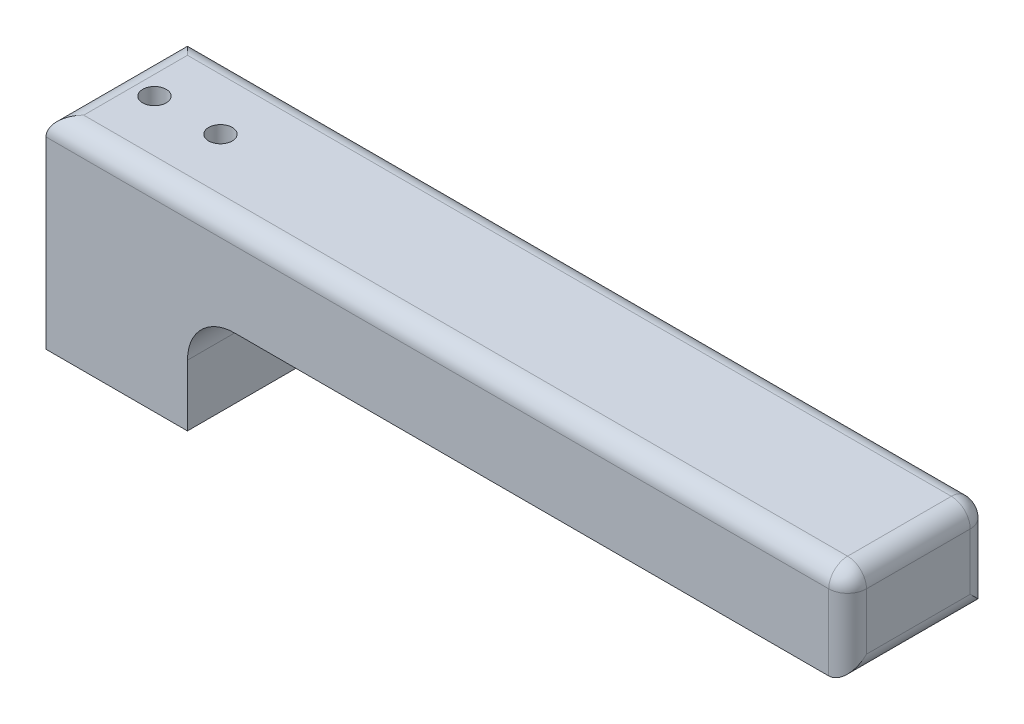
SolidWorks part; units mm, degrees
ref_plane "Front Plane" through (0, 0, 0) normal (0, 0, 1) x (1, 0, 0)
ref_plane "Top Plane" through (0, 0, 0) normal (0, 1, 0) x (1, 0, 0)
ref_plane "Right Plane" through (0, 0, 0) normal (1, 0, 0) x (0, 0, -1)
sketch "Sketch1" plane through (0, 0, 0) normal (0, 0, 1) x (1, 0, 0)
  line L0 (0, 0) -> (0, 21.5)
  line L1 (0, 21.5) -> (85, 21.5)
  line L2 (85, 21.5) -> (85, 11.5)
  line L3 (85, 11.5) -> (15, 11.5)
  line L4 (15, 11.5) -> (15, 0)
  line L5 (15, 0) -> (0, 0)
  dimension "D1" = 11.5
  dimension "D2" = 70
  dimension "D3" = 10
  dimension "D4" = 15
extrude "Boss-Extrude1" add sketch "Sketch1" along normal blind 15
sketch "Sketch2" plane through (0, 0, 0) normal (0, -1, 0) x (1, 0, 0)
  line L0 (0, 0) -> (15, 0) construction
  line L1 (0, 15) -> (0, 0) construction
  circle A0 centre (4, 7.5) radius 1.25
  circle A1 centre (11, 7.5) radius 1.25
  dimension "D3" = 2.5
  dimension "D4" = 2.5
  dimension "D1" = 7.5
  dimension "D2" = 7.5
  dimension "D5" = 4
  dimension "D6" = 7
extrude "Cut-Extrude1" cut sketch "Sketch2" against normal through all
fillet "Fillet1" radius 5 1 edges at (15, 11.5, 7.5)
fillet "Fillet2" radius 2 4 edges at (85, 11.5, 7.5) (85, 16.5, 0) (85, 21.5, 7.5) (85, 16.5, 15)
fillet "Fillet3" radius 2 5 edges at (84.4142, 20.9142, 0.5858) (84.4142, 20.9142, 14.4142) (41.5, 21.5, 0) (0, 21.5, 7.5) (41.5, 21.5, 15)
